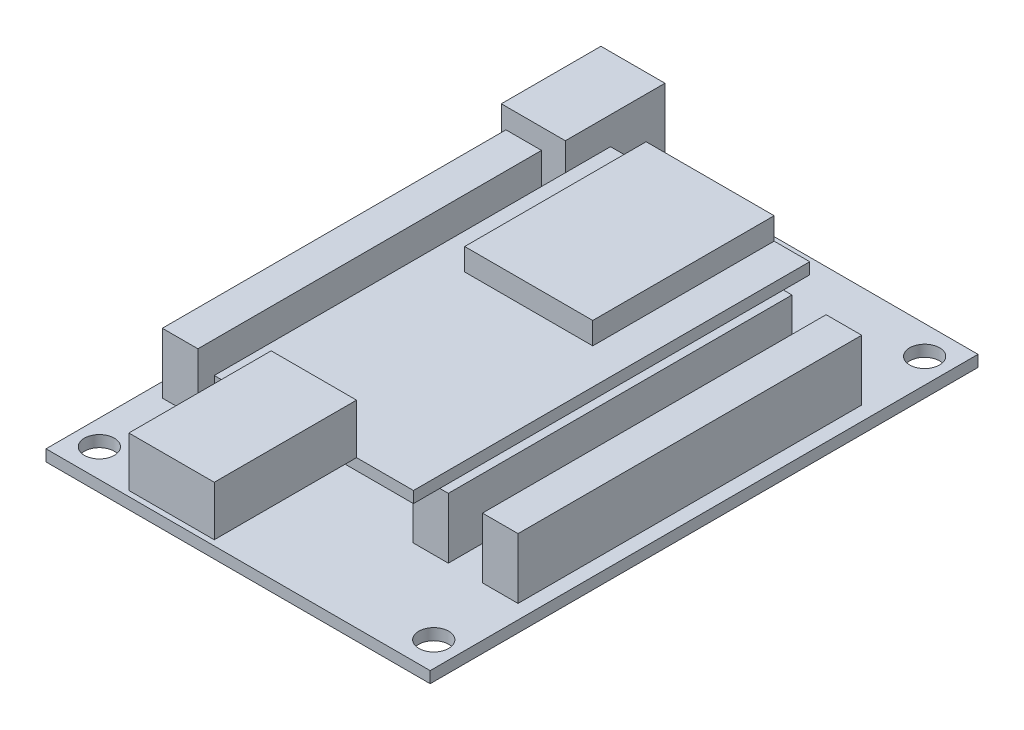
SolidWorks part; units mm, degrees
ref_plane "Front Plane" through (0, 0, 0) normal (0, 0, 1) x (1, 0, 0)
ref_plane "Top Plane" through (0, 0, 0) normal (0, 1, 0) x (1, 0, 0)
ref_plane "Right Plane" through (0, 0, 0) normal (1, 0, 0) x (0, 0, -1)
sketch "SK_Carrier" plane through (0, 0, 0) normal (0, 1, 0) x (1, 0, 0)
  line L1 (-27, 38.5) -> (27, 38.5)
  line L2 (-27, 38.5) -> (-27, -38.5)
  line L3 (-27, -38.5) -> (27, -38.5)
  line L4 (27, 38.5) -> (27, -38.5)
  dimension "D1" = 77
  dimension "D2" = 54
  dimension "D3" = 38.5
  dimension "D4" = 27
extrude "EX_Carrier" add sketch "SK_Carrier" along normal blind 1.6
sketch "SK_MountHoles_4xM4" plane through (0, 0, 0) normal (0, 1, 0) x (1, 0, 0)
  circle A0 centre (23.5, -34.5) radius 2.1
  circle A1 centre (-23.5, -34.5) radius 2.1
  circle A2 centre (23.5, 34.5) radius 2.1
  circle A3 centre (-23.5, 34.5) radius 2.1
  dimension "D3" = 4.2
  dimension "D6" = 4.2
  dimension "D9" = 4.2
  dimension "D12" = 4.2
  dimension "D1" = 34.5
  dimension "D2" = 23.5
  dimension "D4" = 34.5
  dimension "D5" = 23.5
  dimension "D7" = 34.5
  dimension "D8" = 23.5
  dimension "D10" = 34.5
  dimension "D11" = 23.5
extrude "CUT_MountHoles_4xM4" cut sketch "SK_MountHoles_4xM4" along normal blind 1.6
ref_plane "PL_Zp1_6" through (0, 1.6, 0) normal (0, 1, 0) x (1, 0, 0)
sketch "SK_FemaleHeaders" plane through (0, 1.6, 0) normal (0, 1, 0) x (1, 0, 0)
  line L1 (10.2, 24.15) -> (15.2, 24.15)
  line L2 (10.2, 24.15) -> (10.2, -24.15)
  line L3 (10.2, -24.15) -> (15.2, -24.15)
  line L4 (15.2, 24.15) -> (15.2, -24.15)
  line L6 (-15.2, 24.15) -> (-10.2, 24.15)
  line L7 (-15.2, 24.15) -> (-15.2, -24.15)
  line L8 (-15.2, -24.15) -> (-10.2, -24.15)
  line L9 (-10.2, 24.15) -> (-10.2, -24.15)
  dimension "D1" = 48.3
  dimension "D2" = 5
  dimension "D3" = 24.15
  dimension "D4" = 10.2
  dimension "D5" = 48.3
  dimension "D6" = 5
  dimension "D7" = 24.15
  dimension "D8" = 15.2
extrude "EX_FemaleHeaders" add sketch "SK_FemaleHeaders" along normal blind 8.5
sketch "SK_GPIO_Headers" plane through (0, 1.6, 0) normal (0, 1, 0) x (1, 0, 0)
  line L1 (20, 24.15) -> (25, 24.15)
  line L2 (20, 24.15) -> (20, -24.15)
  line L3 (20, -24.15) -> (25, -24.15)
  line L4 (25, 24.15) -> (25, -24.15)
  line L6 (-25, 24.15) -> (-20, 24.15)
  line L7 (-25, 24.15) -> (-25, -24.15)
  line L8 (-25, -24.15) -> (-20, -24.15)
  line L9 (-20, 24.15) -> (-20, -24.15)
  dimension "D1" = 48.3
  dimension "D2" = 5
  dimension "D3" = 24.15
  dimension "D4" = 20
  dimension "D5" = 48.3
  dimension "D6" = 5
  dimension "D7" = 24.15
  dimension "D8" = 25
extrude "EX_GPIO_Headers" add sketch "SK_GPIO_Headers" along normal blind 8.5
sketch "SK_DC_Jack" plane through (0, 1.6, 0) normal (0, 1, 0) x (1, 0, 0)
  line L1 (-26, 38.5) -> (-17, 38.5)
  line L2 (-26, 38.5) -> (-26, 24.5)
  line L3 (-26, 24.5) -> (-17, 24.5)
  line L4 (-17, 38.5) -> (-17, 24.5)
  dimension "D1" = 14
  dimension "D2" = 9
  dimension "D3" = 38.5
  dimension "D4" = 26
extrude "EX_DC_Jack" add sketch "SK_DC_Jack" along normal blind 11
ref_plane "PL_Zp10_1" through (0, 10.1, 0) normal (0, 1, 0) x (1, 0, 0)
sketch "SK_DevKit" plane through (0, 10.1, 0) normal (0, 1, 0) x (1, 0, 0)
  line L1 (-14, 27.85) -> (14, 27.85)
  line L2 (-14, 27.85) -> (-14, -27.85)
  line L3 (-14, -27.85) -> (14, -27.85)
  line L4 (14, 27.85) -> (14, -27.85)
  dimension "D1" = 55.7
  dimension "D2" = 28
  dimension "D3" = 27.85
  dimension "D4" = 14
extrude "EX_DevKit" add sketch "SK_DevKit" along normal blind 1.6
ref_plane "PL_Zp11_7" through (0, 11.7, 0) normal (0, 1, 0) x (1, 0, 0)
sketch "SK_WROOM_Module" plane through (0, 11.7, 0) normal (0, 1, 0) x (1, 0, 0)
  line L1 (-9, 27.85) -> (9, 27.85)
  line L2 (-9, 27.85) -> (-9, 2.35)
  line L3 (-9, 2.35) -> (9, 2.35)
  line L4 (9, 27.85) -> (9, 2.35)
  dimension "D1" = 25.5
  dimension "D2" = 18
  dimension "D3" = 27.85
  dimension "D4" = 9
extrude "EX_WROOM_Module" add sketch "SK_WROOM_Module" along normal blind 3.1
sketch "SK_KeepOut_USB_C" plane through (0, 11.7, 0) normal (0, 1, 0) x (1, 0, 0)
  line L1 (-6, -27.85) -> (6, -27.85)
  line L2 (-6, -27.85) -> (-6, -47.85)
  line L3 (-6, -47.85) -> (6, -47.85)
  line L4 (6, -27.85) -> (6, -47.85)
  dimension "D1" = 20
  dimension "D2" = 12
  dimension "D3" = 27.85
  dimension "D4" = 6
extrude "EX_KeepOut_USB_C" add sketch "SK_KeepOut_USB_C" along normal blind 7
ref_axis "AX_X" through (0, 0, -42.8175) along (0, 0, 1)
ref_axis "AX_Y" through (29.7, 0, 0) along (-1, 0, 0)
ref_axis "AX_Z" through (0, 19.635, 0) along (0, -1, 0)
